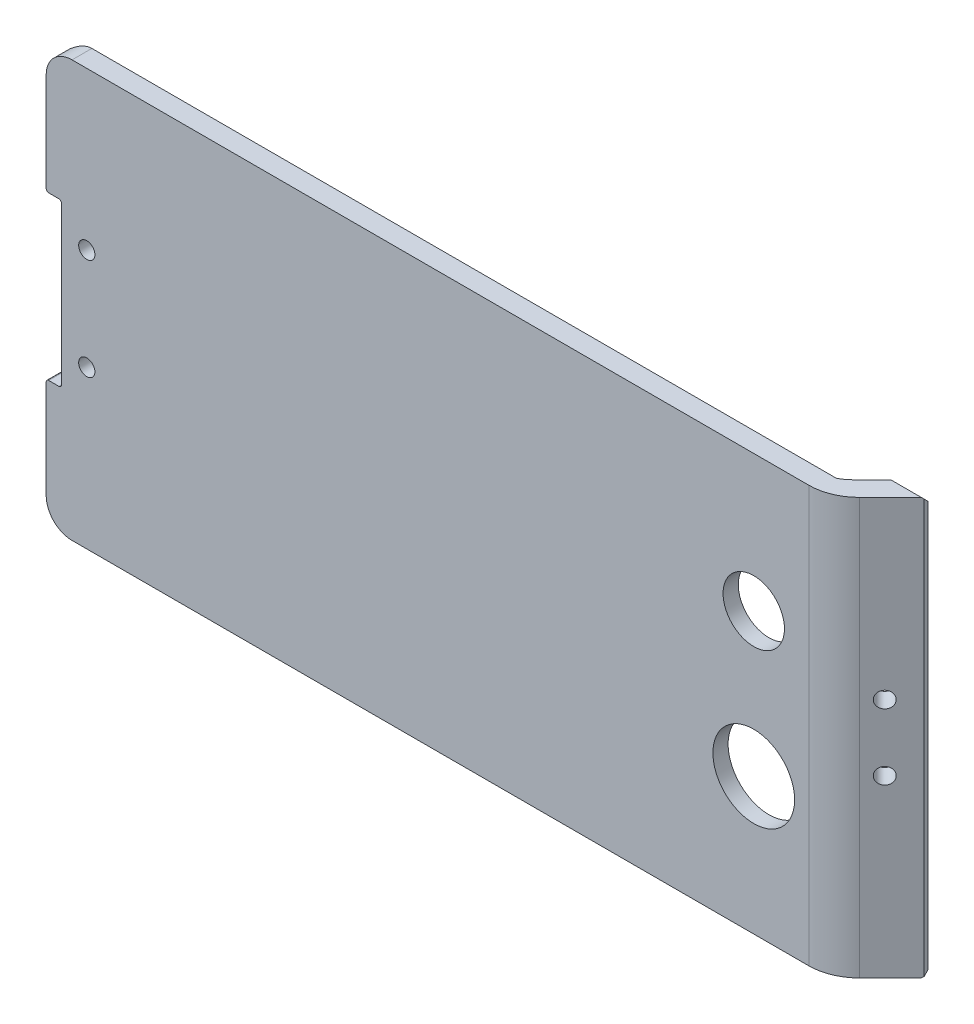
SolidWorks part; units mm, degrees
ref_plane "前视基准面" through (0, 0, 0) normal (1, 0, 0) x (0, 1, 0)
ref_plane "上视基准面" through (0, 0, 0) normal (0, 0, 1) x (0, 1, 0)
ref_plane "右视基准面" through (0, 0, 0) normal (0, 1, 0) x (-1, 0, 0)
other "Configuration Table"
sketch "草图1" plane through (0, 0, 0) normal (0, 0, 1) x (0, 1, 0)
  line L1 (0, 0) -> (88.2, 0)
  line L2 (0, 0) -> (0, -177)
  line L3 (0, -177) -> (88.2, -177)
  line L4 (88.2, 0) -> (88.2, -177)
  dimension "D1" = 177
  dimension "D2" = 88.2
extrude "凸台-拉伸1" add sketch "草图1" along normal blind 52.9
chamfer "倒角1" [suppressed] distance 1 angle 45
shell "抽壳1" thickness 3 removed face at (88.5, 44.1, 0)
sketch "草图4" [suppressed] plane through (0, 0, 52.9) normal (0, 0, 1) x (1, 0, 0)
  line L0 (164, 0) -> (0, 0) construction
  line L1 (1.5, 64) -> (101.5, 64)
  line L2 (1.5, 64) -> (1.5, 7.5)
  line L3 (1.5, 7.5) -> (101.5, 7.5)
  line L4 (101.5, 64) -> (101.5, 7.5)
  line L5 (0, 0) -> (0, 86) construction
  line L6 (0, 86) -> (164, 86) construction
  dimension "D1" = 7.5
  dimension "D2" = 1.5
  dimension "D3" = 22
  dimension "D4" = 100
extrude "切除-拉伸3" [suppressed] cut sketch "草图4" against normal up to next
sketch "草图9" plane through (0, 0, 0) normal (0, -1, 0) x (1, 0, 0)
  line L0 (0, 5.9) -> (71.5, 5.9)
  line L1 (0, 52.9) -> (0, 0) construction
  line L2 (71.5, 5.9) -> (71.5, 2.9)
  line L3 (71.5, 2.9) -> (68.5, 2.9)
  line L4 (68.5, 2.9) -> (68.5, 0)
  line L5 (0, 0) -> (177, 0) construction
  line L6 (0, 5.9) -> (0, 0)
  line L7 (108.5, 0) -> (108.5, 2.9)
  line L8 (108.5, 2.9) -> (105.5, 2.9)
  line L9 (105.5, 2.9) -> (105.5, 5.9)
  line L10 (105.5, 5.9) -> (177, 5.9)
  line L11 (177, 52.9) -> (177, 0) construction
  line L12 (0, 0) -> (68.5, 0)
  line L13 (108.5, 0) -> (177, 0)
  line L14 (177, 0) -> (177, 5.9)
  point P16 (88.5, 0)
  dimension "D1" = 17
  dimension "D2" = 17
  dimension "D3" = 20
  dimension "D4" = 20
  dimension "D5" = 3
  dimension "D6" = 3
  dimension "D7" = 2.9
  dimension "D8" = 2.9
extrude "切除-拉伸4" [suppressed] cut sketch "草图9" against normal through all
sketch "草图10" [suppressed] plane through (0, 0, 0) normal (0, -1, 0) x (1, 0, 0)
  line L0 (64.75, 5.9) -> (98.75, 5.9)
  line L1 (98.75, 5.9) -> (98.75, 2.9)
  line L2 (98.75, 2.9) -> (101.75, 2.9)
  line L3 (101.75, 2.9) -> (101.75, 0)
  line L4 (101.75, 0) -> (61.75, 0)
  line L5 (61.75, 0) -> (61.75, 2.9)
  line L6 (61.75, 2.9) -> (64.75, 2.9)
  line L7 (64.75, 2.9) -> (64.75, 5.9)
extrude "凸台-拉伸4" [suppressed] add sketch "草图10" along normal blind 3
sketch "草图11" [suppressed] plane through (0, 86, 0) normal (0, 1, 0) x (-1, 0, 0)
  line L0 (-99, 5.9) -> (-65, 5.9)
  line L1 (-65, 5.9) -> (-65, 2.9)
  line L2 (-65, 2.9) -> (-62, 2.9)
  line L3 (-62, 2.9) -> (-62, 0)
  line L4 (-62, 0) -> (-102, 0)
  line L5 (-102, 0) -> (-102, 2.9)
  line L6 (-102, 2.9) -> (-99, 2.9)
  line L7 (-99, 2.9) -> (-99, 5.9)
extrude "凸台-拉伸5" [suppressed] add sketch "草图11" along normal blind 3
chamfer "倒角5" [suppressed] distance 5 angle 45
fillet "圆角1" [suppressed] radius 1
sketch "草图12" [suppressed] plane through (0, -3, 0) normal (0, -1, 0) x (1, 0, 0)
  line L0 (56.5, 2.9) -> (93.5, 2.9) construction
  line L1 (57, 2.9) -> (56, 2.9) construction
  line L2 (94, 2.9) -> (93, 2.9) construction
  point P6 (65, 2.9)
  point P7 (85, 2.9)
  point P8 (75, 2.9)
  dimension "D1" = 10
  dimension "D2" = 10
hole_wizard "M3 六角圆柱头螺钉的柱形沉头孔4" [suppressed] positions "草图12" profile "草图13" counterbore size "M3" standard "GB"
sketch "草图13" plane through (85, -3, 2.9) normal (1, 0, 0) x (0, 0, -1)
  line L0 (0, 0) -> (0, 6)
  line L1 (0, 6) -> (1.6, 6)
  line L3 (1.6, 6) -> (1.6, 3.4)
  line L4 (1.6, 3.4) -> (3, 3.4)
  line L5 (3, 3.4) -> (3, 0)
  line L7 (3, 0) -> (0, 0)
  line L11 (0, -6.35) -> (0, 107.95) construction
  dimension "通孔孔直径" = 3.2
  dimension "通孔孔深度" = 6
  dimension "柱形沉头孔直径" = 6
  dimension "柱形沉头孔深度" = 3.4
fillet "圆角2" [suppressed] radius 1
sketch "草图14" [suppressed] plane through (0, 89, 0) normal (0, 1, 0) x (-1, 0, 0)
  line L0 (-93.5, 2.9) -> (-56.5, 2.9) construction
  line L1 (-93, 2.9) -> (-94, 2.9) construction
  line L2 (-56, 2.9) -> (-57, 2.9) construction
  point P6 (-85, 2.9)
  point P7 (-65, 2.9)
  point P8 (-75, 2.9)
  dimension "D1" = 10
  dimension "D2" = 10
hole_wizard "M3 六角圆柱头螺钉的柱形沉头孔5" [suppressed] positions "草图14" profile "草图15" counterbore size "M3" standard "GB"
sketch "草图15" plane through (65, 89, 2.9) normal (1, 0, 0) x (0, 0, 1)
  line L0 (0, 0) -> (0, 6)
  line L1 (0, 6) -> (1.6, 6)
  line L3 (1.6, 6) -> (1.6, 3.4)
  line L4 (1.6, 3.4) -> (3, 3.4)
  line L5 (3, 3.4) -> (3, 0)
  line L7 (3, 0) -> (0, 0)
  line L11 (0, -6.35) -> (0, 107.95) construction
  dimension "通孔孔直径" = 3.2
  dimension "通孔孔深度" = 6
  dimension "柱形沉头孔直径" = 6
  dimension "柱形沉头孔深度" = 3.4
sketch "草图16" plane through (0, 0, 52.9) normal (0, 0, 1) x (1, 0, 0)
  line L0 (152, 88.2) -> (152, 0) construction
  line L1 (177, 88.2) -> (0, 88.2) construction
  line L2 (0, 0) -> (177, 0) construction
  line L3 (177, 0) -> (177, 88.2) construction
  circle A0 centre (152, 58.2) radius 6.05
  circle A1 centre (152, 30) radius 8.05
  dimension "D1" = 12.1
  dimension "D2" = 16.1
  dimension "D3" = 25
  dimension "D4" = 30
  dimension "D5" = 30
extrude "切除-拉伸5" cut sketch "草图16" against normal up to next
sketch "草图18" [suppressed] plane through (0, 0, 0) normal (-1, 0, 0) x (0, 0, 1)
  line L0 (5.9, 44.1) -> (52.9, 44.1) construction
  line L1 (5.9, 88.2) -> (5.9, 0) construction
  line L2 (52.9, 88.2) -> (52.9, 0) construction
  line L3 (5.9, 85.1) -> (45.9, 85.1)
  line L4 (45.9, 85.1) -> (45.9, 3.1)
  line L5 (45.9, 3.1) -> (5.9, 3.1)
  line L6 (5.9, 3.1) -> (5.9, 85.1)
  dimension "D1" = 41
  dimension "D2" = 41
  dimension "D3" = 40
extrude "切除-拉伸6" [suppressed] cut sketch "草图18" against normal blind 10
chamfer "倒角6" [suppressed] distance 1 angle 45
sketch "草图19" plane through (0, 0, 52.9) normal (0, 0, 1) x (1, 0, 0)
  line L0 (0, 88.2) -> (0, 0) construction
  line L1 (0, 0) -> (177, 0) construction
  circle A0 centre (86, 31) radius 12.5
  dimension "D3" = 25
  dimension "D1" = 86
  dimension "D2" = 31
extrude "切除-拉伸7" [suppressed] cut sketch "草图19" against normal up to next
chamfer "倒角7" distance 10 angle 45 2 edges at (177, 44.1, 52.9) (174, 44.1, 49.9)
chamfer "倒角8" distance 1 angle 45 8 edges at (83.5, 85.2, 49.9) (83.5, 3, 49.9) (177, 0, 21.45) (172, 0, 47.9) (83.5, 0, 52.9) (177, 88.2, 21.45) (172, 88.2, 47.9) (83.5, 88.2, 52.9)
sketch "草图21" plane through (0, 0, 0) normal (0, 0, -1) x (-1, 0, 0)
  line L0 (-3, 3) -> (-174, 3) construction
  line L1 (-174, 85.2) -> (-163.5, 85.2)
  line L2 (-174, 85.2) -> (-174, 3)
  line L3 (-174, 3) -> (-163.5, 3)
  line L4 (-163.5, 85.2) -> (-163.5, 3)
  line L6 (-3, 85.2) -> (-13.5, 85.2)
  line L7 (-3, 85.2) -> (-3, 3)
  line L8 (-3, 3) -> (-13.5, 3)
  line L9 (-13.5, 85.2) -> (-13.5, 3)
  dimension "D1" = 10.5
  dimension "D2" = 10.5
extrude "凸台-拉伸7" add sketch "草图21" against normal blind 6
sketch "草图22" plane through (0, 0, 52.9) normal (0, 0, 1) x (1, 0, 0)
  line L0 (177, 87.2) -> (177, 1) construction
  line L1 (12.6, 85.1) -> (177, 85.1)
  line L2 (12.6, 85.1) -> (12.6, 3.1)
  line L3 (12.6, 3.1) -> (177, 3.1)
  line L4 (177, 85.1) -> (177, 3.1)
  line L5 (0, 88.2) -> (166.5858, 88.2) construction
  line L6 (166.5858, 0) -> (0, 0) construction
  line L7 (0, 87.2) -> (0, 1) construction
  dimension "D1" = 3.1
  dimension "D2" = 3.1
  dimension "D3" = 12.6
extrude "切除-拉伸8" cut sketch "草图22" against normal blind 10 flip side to cut
sketch "草图23" plane through (0, 0, 0) normal (0, -1, 0) x (1, 0, 0)
  line L1 (0, 42.9) -> (177, 42.9)
  line L2 (0, 42.9) -> (0, 0)
  line L3 (0, 0) -> (177, 0)
  line L4 (177, 42.9) -> (177, 0)
extrude "切除-拉伸9" cut sketch "草图23" against normal through all
fillet "圆角3" radius 10 1 edges at (167, 44.1, 52.9)
fillet "圆角4" radius 5.1 2 edges at (12.6, 3.1, 50.95) (12.6, 85.1, 50.95)
chamfer "倒角9" [suppressed] distance 0.5 angle 45
sketch "草图24" plane through (109.95, 0, 109.95) normal (0.7071, 0, 0.7071) x (0.7071, 0, -0.7071)
  line L0 (94.823, 85.1) -> (94.823, 3.1) construction
  circle A0 centre (88.323, 50.6) radius 1.6
  circle A1 centre (88.323, 37.6) radius 1.6
  point P6 (94.823, 44.1)
  dimension "D3" = 3.2
  dimension "D4" = 3.2
  dimension "D1" = 13
  dimension "D2" = 6.5
  dimension "D5" = 6.5
  dimension "D6" = 6.5
extrude "切除-拉伸10" cut sketch "草图24" against normal through all
chamfer "倒角10" distance 1 angle 45 3 edges at (174, 85.1, 42.9) (174, 3.1, 42.9) (177, 44.1, 42.9) first distance on face at (125.9112, 85.1, 48.6106) first distance on face at (125.9112, 3.1, 48.6106) first distance on face at (173.5352, 50.6, 46.3648)
sketch "草图25" plane through (0, 0, 52.9) normal (0, 0, 1) x (1, 0, 0)
  line L0 (12.6, 80) -> (12.6, 8.2) construction
  circle A0 centre (20.6, 54.1) radius 1.6
  circle A1 centre (20.6, 34.1) radius 1.6
  point P6 (12.6, 44.1)
  dimension "D3" = 3.2
  dimension "D4" = 3.2
  dimension "D1" = 8
  dimension "D2" = 8
  dimension "D5" = 10
  dimension "D6" = 10
extrude "切除-拉伸11" cut sketch "草图25" against normal up to next
fillet "圆角5" radius 8 1 edges at (164, 44.1, 49.9)
sketch "草图26" plane through (0, 0, 52.9) normal (0, 0, 1) x (1, 0, 0)
  line L0 (12.6, 80) -> (12.6, 8.2) construction
  line L1 (12.6, 60.1) -> (15.6, 60.1)
  line L2 (12.6, 60.1) -> (12.6, 28.1)
  line L3 (12.6, 28.1) -> (15.6, 28.1)
  line L4 (15.6, 60.1) -> (15.6, 28.1)
  point P7 (12.6, 44.1)
  dimension "D1" = 3
  dimension "D2" = 16
  dimension "D3" = 32
extrude "切除-拉伸12" cut sketch "草图26" against normal up to next
fillet "圆角6" radius 0.5 4 edges at (12.6, 28.1, 51.4) (15.6, 28.1, 51.4) (15.6, 60.1, 51.4) (12.6, 60.1, 51.4)
